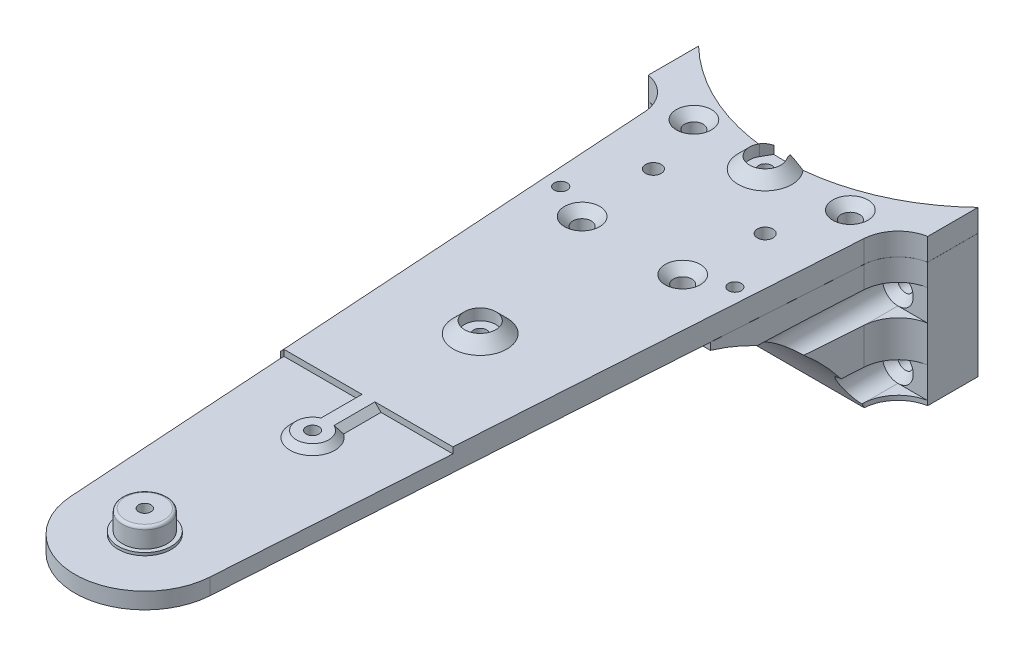
SolidWorks part; units mm, degrees
ref_plane "Front Plane" through (0, 0, 0) normal (0, 0, 1) x (1, 0, 0)
ref_plane "Top Plane" through (0, 0, 0) normal (0, 1, 0) x (1, 0, 0)
ref_plane "Right Plane" through (0, 0, 0) normal (1, 0, 0) x (0, 0, -1)
sketch "Sketch1" plane through (0, 0, 0) normal (0, 1, 0) x (1, 0, 0)
  line L0 (0, 0) -> (0, -150) construction
  line L1 (-22.2029, -1.4463) -> (-12.4736, -150.8125) construction
  line L2 (22.2029, -1.4462) -> (12.4736, -150.8125) construction
  line L3 (-12.4736, -150.8125) -> (-19.6328, -40.9037)
  line L4 (12.4736, -150.8125) -> (19.6328, -40.9037)
  line L5 (-25, -25.9037) -> (25, -25.9037) construction
  line L6 (-25, -25.9037) -> (-25, -34.9037)
  line L7 (25, -25.9037) -> (25, -34.9037)
  circle A0 centre (0, 0) radius 36 construction
  arc A1 (-12.4736, -150.8125) -> (12.4736, -150.8125) centre (0, -150) ccw
  circle A2 centre (0, 0) radius 19.5 construction
  circle A3 centre (0, 19.5) radius 2.75 construction
  circle A4 centre (0, 0) radius 22.25 construction
  arc A5 (-25, -25.9037) -> (25, -25.9037) centre (0, 0) ccw
  arc A6 (-25, -34.9037) -> (-19.6328, -40.9037) centre (-26.1442, -41.3278) cw
  arc A7 (25, -34.9037) -> (19.6328, -40.9037) centre (26.1442, -41.3278) ccw
  dimension "D1" = 72
  dimension "D3" = 25
  dimension "D4" = 39
  dimension "D5" = 5.5
  dimension "D2" = 150
  dimension "D6" = 50
  dimension "D7" = 9
  dimension "D8" = 15
extrude "Boss-Extrude1" add sketch "Sketch1" against normal blind 4
sketch "Sketch2" plane through (0, -4, 0) normal (0, -1, 0) x (1, 0, 0)
  line L0 (25, 34.9037) -> (25, 25.9037) construction
  line L1 (-25, 25.9037) -> (-25, 34.9037) construction
  line L2 (25, 34.9037) -> (25, 25.9037)
  line L3 (-25, 25.9037) -> (-25, 34.9037)
  line L4 (-19.6328, 40.9037) -> (19.6328, 40.9037)
  arc A0 (19.6328, 40.9037) -> (25, 34.9037) centre (26.1442, 41.3278) ccw construction
  arc A1 (25, 25.9037) -> (-25, 25.9037) centre (0, 0) ccw construction
  arc A2 (-25, 34.9037) -> (-19.6328, 40.9037) centre (-26.1442, 41.3278) ccw construction
  arc A3 (19.6328, 40.9037) -> (25, 34.9037) centre (26.1442, 41.3278) ccw
  arc A4 (25, 25.9037) -> (-25, 25.9037) centre (0, 0) ccw
  arc A5 (-25, 34.9037) -> (-19.6328, 40.9037) centre (-26.1442, 41.3278) ccw
extrude "Boss-Extrude2" add sketch "Sketch2" along normal offset from surface (22.2378 mm away) 26.2378 up to face at (0, 0, 65.6223)
ref_plane "Plane1" through (0, 0, 34.9037) normal (0, 0, 1) x (1, 0, 0)
fillet "Fillet2" radius 40 1 edges at (0, -4, 40.9037)
sketch "Sketch3" plane through (0, 0, 34.9037) normal (0, 0, 1) x (1, 0, 0)
  line L0 (25, 0) -> (-25, 0) construction
  line L1 (-19.6636, -22.6878) -> (19.6636, -22.6878) construction
  line L2 (-19.6636, -22.6878) -> (-19.6636, -10.6878) construction
  line L3 (-19.6636, -10.6878) -> (19.6636, -10.6878) construction
  line L4 (19.6636, -22.6878) -> (19.6636, -10.6878) construction
  line L5 (-19.6636, -22.6878) -> (19.6636, -10.6878) construction
  line L6 (-19.6636, -10.6878) -> (19.6636, -22.6878) construction
  line L7 (-19.6636, -7.9378) -> (-25, -7.9378)
  line L8 (-25, -7.9378) -> (-25, -13.4378)
  line L9 (-25, -13.4378) -> (-19.6636, -13.4378)
  line L10 (-25, -26.2378) -> (-25, 0) construction
  line L11 (0, -16.6878) -> (-25, -16.6878) construction
  line L12 (-25, -25.4378) -> (-25, -19.9378)
  line L13 (-25, -19.9378) -> (-19.6636, -19.9378)
  line L14 (-19.6636, -25.4378) -> (-25, -25.4378)
  line L15 (0, -16.6878) -> (0, 0) construction
  line L16 (19.6636, -25.4378) -> (25, -25.4378)
  line L17 (25, -19.9378) -> (19.6636, -19.9378)
  line L18 (25, -25.4378) -> (25, -19.9378)
  line L19 (25, -13.4378) -> (19.6636, -13.4378)
  line L20 (25, -7.9378) -> (25, -13.4378)
  line L21 (19.6636, -7.9378) -> (25, -7.9378)
  arc A0 (-19.6636, -13.4378) -> (-19.6636, -7.9378) centre (-19.6636, -10.6878) ccw
  arc A4 (-19.6636, -19.9378) -> (-19.6636, -25.4378) centre (-19.6636, -22.6878) cw
  arc A5 (19.6636, -19.9378) -> (19.6636, -25.4378) centre (19.6636, -22.6878) ccw
  arc A6 (19.6636, -13.4378) -> (19.6636, -7.9378) centre (19.6636, -10.6878) cw
  point P0 (0, -16.6878)
  dimension "D4" = 5.5
  dimension "D1" = 10.6878
  dimension "D2" = 12
  dimension "D3" = 39.3272
extrude "Cut-Extrude1" cut sketch "Sketch3" along normal through all
chamfer "Chamfer1" [suppressed] distance 2.75 angle 60
hole_wizard "CSK for M2.5 Flat Head Machine Screw1" positions "Sketch5" profile "Sketch6" countersink size "M2.5" standard "ANSI Metric" end condition through all
sketch "Sketch5" plane through (0, 0, 34.9037) normal (0, 0, 1) x (1, 0, 0)
  point P0 (19.6636, -22.6878)
  point P3 (-19.6636, -22.6878)
  point P6 (-19.6636, -10.6878)
  point P9 (19.6636, -10.6878)
sketch "Sketch6" plane through (19.6636, -22.6878, 34.9037) normal (1, 0, 0) x (0, -1, 0)
  line L0 (0, 0) -> (0, 9)
  line L1 (0, 9) -> (1.4, 9)
  line L2 (1.4, 9) -> (1.4, 1.35)
  line L3 (1.4, 1.35) -> (2.75, 0)
  line L5 (2.75, 0) -> (0, 0)
  line L6 (-1.4, 1.35) -> (-2.75, 0) construction
  line L11 (0, -6.35) -> (0, 107.95) construction
  dimension "Thru Hole Dia." = 2.8
  dimension "Thru Hole Depth" = 9
  dimension "Near C'Sink Dia." = 5.5
  dimension "Near C'Sink Angle" = 90
sketch "Sketch8" plane through (0, 0, 0) normal (0, 1, 0) x (1, 0, 0)
  line L1 (1.0164, -92.5616) -> (1.0209, -117.4381) construction
  line L2 (-0.9836, -92.5619) -> (-0.9791, -117.4384) construction
  line L3 (15.1322, -109.9973) -> (15.1322, -176.6324)
  line L4 (15.1322, -176.6324) -> (-15.0896, -176.6324)
  line L5 (-15.0896, -176.6324) -> (-15.0896, -109.9973)
  line L29 (-0.9805, -109.9973) -> (-0.9791, -117.4384)
  line L30 (1.0195, -109.9973) -> (1.0209, -117.4381)
  line L31 (1.0195, -109.9973) -> (15.1322, -109.9973)
  line L72 (-15.0896, -109.9973) -> (-0.9805, -109.9973)
  arc A4 (-0.9791, -117.4384) -> (1.0209, -117.4381) centre (0.0213, -120) ccw construction
  arc A8 (-0.9791, -117.4384) -> (1.0209, -117.4381) centre (0.0213, -120) ccw
  point P0 (0.0213, -176.6324)
  dimension "D2" = 5.5
extrude "Cut-Extrude3" cut sketch "Sketch8" against normal blind 1.09
sketch "Sketch9" plane through (0, -4, 0) normal (0, -1, 0) x (1, 0, 0)
  line L0 (-17.2982, 76.7436) -> (17.2982, 76.7436)
  line L1 (17.2982, 76.7436) -> (17.9496, 66.7436)
  line L2 (17.9496, 66.7436) -> (-17.9496, 66.7436)
  line L3 (-17.9496, 66.7436) -> (-17.2982, 76.7436)
  line L4 (-17.2982, 76.7436) -> (-12.4736, 150.8125) construction
  line L5 (12.4736, 150.8125) -> (17.2982, 76.7436) construction
  dimension "D1" = 10
extrude "Cut-Extrude4" cut sketch "Sketch9" along normal through all
sketch "Sketch11" plane through (0, -4, 0) normal (0, -1, 0) x (1, 0, 0)
  circle A0 centre (0, 0) radius 161
extrude "Cut-Extrude5" cut sketch "Sketch11" along normal blind 0.01
sketch "Sketch12" plane through (0, 0, 0) normal (0, 1, 0) x (1, 0, 0)
  line L0 (-17.9496, -66.7436) -> (17.9496, -66.7436) construction
  line L1 (-17.9496, -66.7436) -> (17.9496, -66.7436) construction
  line L3 (-9, -62.7436) -> (9, -62.7436) construction
  line L4 (-9, -62.7436) -> (-14, -37.7436) construction
  line L5 (-14, -37.7436) -> (14, -37.7436) construction
  line L6 (9, -62.7436) -> (14, -37.7436) construction
  line L7 (-9, -62.7436) -> (14, -37.7436) construction
  line L8 (-14, -37.7436) -> (9, -62.7436) construction
  circle A0 centre (-14, -37.7436) radius 1.65
  circle A1 centre (14, -37.7436) radius 1.65
  circle A2 centre (-9, -62.7436) radius 1.65
  circle A3 centre (9, -62.7436) radius 1.65
  point P2 (0, -52.961)
  point P15 (0, -62.7436)
  dimension "D1" = 3.3
  dimension "D2" = 4
  dimension "D3" = 28
  dimension "D4" = 25
  dimension "D5" = 18
extrude "Cut-Extrude6" cut sketch "Sketch12" against normal blind 8.25
ref_plane "Plane2" through (0, -5.2702, 0) normal (0, 1, 0) x (1, 0, 0)
sketch "Sketch13" plane through (0, -5.2702, 0) normal (0, 1, 0) x (1, 0, 0)
  line L0 (0, 0) -> (0, -36) construction
  line L1 (-11.75, -59.9936) -> (-6.25, -59.9936)
  line L2 (-11.75, -59.9936) -> (-11.75, -65.4936)
  line L3 (-11.75, -65.4936) -> (-6.25, -65.4936) construction
  line L4 (-6.25, -59.9936) -> (-6.25, -65.4936)
  line L5 (-11.75, -59.9936) -> (-6.25, -65.4936) construction
  line L6 (-11.75, -65.4936) -> (-6.25, -59.9936) construction
  line L7 (-6.25, -65.4936) -> (-6.25, -66.7436)
  line L8 (-17.9496, -66.7436) -> (17.9496, -66.7436) construction
  line L9 (-6.25, -66.7436) -> (-11.75, -66.7436)
  line L10 (-11.75, -66.7436) -> (-11.75, -65.4936)
  line L11 (6.25, -66.7436) -> (11.75, -66.7436)
  line L12 (6.25, -65.4936) -> (6.25, -66.7436)
  line L13 (6.25, -59.9936) -> (6.25, -65.4936)
  line L14 (11.75, -59.9936) -> (6.25, -59.9936)
  line L15 (11.75, -59.9936) -> (11.75, -65.4936)
  line L16 (11.75, -66.7436) -> (11.75, -65.4936)
  arc A0 (-25, -25.9037) -> (25, -25.9037) centre (0, 0) ccw construction
  point P0 (-9, -62.7436)
  dimension "D1" = 5.5
extrude "Cut-Extrude7" cut sketch "Sketch13" against normal blind 8.5
sketch "Sketch14" plane through (0, -8.25, 0) normal (0, 1, 0) x (1, 0, 0)
  line L0 (0, 0) -> (0, -36) construction
  line L1 (-14, -37.7436) -> (0, 0) construction
  line L2 (-15.681, -34.0804) -> (-10.3368, -36.0627) construction
  line L3 (-15.681, -34.0804) -> (-17.6632, -39.4246)
  line L4 (-17.6632, -39.4246) -> (-12.319, -41.4069)
  line L5 (-10.3368, -36.0627) -> (-12.319, -41.4069)
  line L6 (-15.681, -34.0804) -> (-12.319, -41.4069) construction
  line L7 (-17.6632, -39.4246) -> (-10.3368, -36.0627) construction
  line L8 (-15.681, -34.0804) -> (-15.1525, -32.6558)
  line L9 (-15.1525, -32.6558) -> (-9.8083, -34.6381)
  line L10 (-9.8083, -34.6381) -> (-10.3368, -36.0627)
  line L11 (15.1525, -32.6558) -> (9.8083, -34.6381)
  line L12 (15.681, -34.0804) -> (15.1525, -32.6558)
  line L13 (15.681, -34.0804) -> (17.6632, -39.4246)
  line L14 (17.6632, -39.4246) -> (12.319, -41.4069)
  line L15 (10.3368, -36.0627) -> (12.319, -41.4069)
  line L16 (9.8083, -34.6381) -> (10.3368, -36.0627)
  arc A0 (-25, -25.9037) -> (25, -25.9037) centre (0, 0) ccw construction
  point P6 (-14, -37.7436)
  dimension "D1" = 5.7
extrude "Cut-Extrude8" cut sketch "Sketch14" along normal blind 2
hole_wizard "CSK for M3 Flat Head Machine Screw1" positions "Sketch15" profile "Sketch16" countersink size "M3" standard "ANSI Metric"
sketch "Sketch15" plane through (0, 0, 0) normal (0, 1, 0) x (1, 0, 0)
  point P0 (-14, -37.7436)
  point P3 (14, -37.7436)
  point P6 (9, -62.7436)
  point P9 (-9, -62.7436)
sketch "Sketch16" plane through (-14, 0, 37.7436) normal (1, 0, 0) x (0, 0, 1)
  line L0 (0, 0) -> (0, 8.9914)
  line L1 (0, 8.9914) -> (1.65, 8)
  line L2 (1.65, 8) -> (1.65, 1.5)
  line L3 (1.65, 1.5) -> (3.15, 0)
  line L5 (3.15, 0) -> (0, 0)
  line L6 (-1.65, 1.5) -> (-3.15, 0) construction
  line L10 (0, 8.9914) -> (-1.65, 8) construction
  line L11 (0, -6.35) -> (0, 107.95) construction
  dimension "Hole Dia." = 3.3
  dimension "Hole Depth" = 8
  dimension "Near C'Sink Dia." = 6.3
  dimension "Near C'Sink Angle" = 90
  dimension "Drill Angle" = 118
sketch "Sketch18" plane through (0, -4, 0) normal (0, -1, 0) x (1, 0, 0)
  circle A1 centre (0.0071, 39) radius 2.75
  circle A2 centre (0.0071, 39) radius 2.75 construction
  circle A3 centre (0.016, 90) radius 2.8 construction
  arc A5 (1.0209, 117.4381) -> (-0.9791, 117.4384) centre (0.0213, 120) ccw construction
  circle A9 centre (-15.5725, 60.0029) radius 1.15
  circle A11 centre (-15.5725, 60.0029) radius 2.75
  circle A12 centre (-15.5725, 60.0029) radius 2.75 construction
  circle A13 centre (15.5944, 59.9971) radius 1.15
  circle A15 centre (0.0071, 39) radius 1.15
  circle A17 centre (15.5944, 59.9971) radius 2.75
  circle A18 centre (15.5944, 59.9971) radius 2.75 construction
  arc A19 (1.0209, 117.4381) -> (-0.9791, 117.4384) centre (0.0213, 120) ccw construction
  circle A20 centre (0.0213, 120) radius 1.15
  circle A21 centre (0.016, 90) radius 2.8 construction
  circle A22 centre (0.016, 90) radius 1.15
  dimension "D2" = 2.3
  dimension "D1" = 0
  dimension "D6" = 0
  dimension "D9" = 0
extrude "Cut-Extrude9" cut sketch "Sketch18" against normal through all
sketch "Sketch19" plane through (0, -4, 0) normal (0, -1, 0) x (1, 0, 0)
  line L1 (1.4503, 122.475) -> (-1.4076, 122.475)
  line L2 (-1.4076, 122.475) -> (-2.8366, 120)
  line L3 (-2.8366, 120) -> (-1.4076, 117.525)
  line L4 (-1.4076, 117.525) -> (1.4503, 117.525)
  line L5 (1.4503, 117.525) -> (2.8792, 120)
  line L6 (2.8792, 120) -> (1.4503, 122.475)
  line L7 (1.4449, 92.475) -> (-1.413, 92.475)
  line L8 (-1.413, 92.475) -> (-2.8419, 90)
  line L9 (-2.8419, 90) -> (-1.413, 87.525)
  line L10 (-1.413, 87.525) -> (1.4449, 87.525)
  line L11 (1.4449, 87.525) -> (2.8739, 90)
  line L12 (2.8739, 90) -> (1.4449, 92.475)
  line L13 (-12.7206, 59.8171) -> (-13.9857, 62.3797)
  line L14 (-13.9857, 62.3797) -> (-16.8375, 62.5655)
  line L15 (-16.8375, 62.5655) -> (-18.4243, 60.1886) construction
  line L16 (-18.4243, 60.1886) -> (-17.1593, 57.626) construction
  line L17 (-17.1593, 57.626) -> (-14.3074, 57.4402)
  line L18 (-14.3074, 57.4402) -> (-12.7206, 59.8171)
  line L19 (2.4786, 37.5649) -> (2.4857, 40.4228)
  line L20 (2.4857, 40.4228) -> (0.0143, 41.8579)
  line L21 (0.0143, 41.8579) -> (-2.4643, 40.4351)
  line L22 (-2.4643, 40.4351) -> (-2.4714, 37.5772)
  line L23 (-2.4714, 37.5772) -> (0, 36.1421) construction
  line L24 (0, 36.1421) -> (2.4786, 37.5649) construction
  line L25 (0, 0) -> (0, 162.5) construction
  line L26 (-18.4243, 60.1886) -> (-15.5725, 60.0029) construction
  line L27 (-19.6328, 40.9037) -> (-12.4736, 150.8125) construction
  line L28 (-16.8375, 62.5655) -> (-18.2159, 62.6553)
  line L29 (-18.2159, 62.6553) -> (-18.5377, 57.7158)
  line L30 (-18.5377, 57.7158) -> (-17.1593, 57.626)
  line L31 (18.2159, 62.6553) -> (18.5377, 57.7158)
  line L32 (16.8375, 62.5655) -> (18.2159, 62.6553)
  line L33 (13.9857, 62.3797) -> (16.8375, 62.5655)
  line L34 (12.7206, 59.8171) -> (13.9857, 62.3797)
  line L35 (14.3074, 57.4402) -> (12.7206, 59.8171)
  line L36 (17.1593, 57.626) -> (14.3074, 57.4402)
  line L37 (18.5377, 57.7158) -> (17.1593, 57.626)
  line L38 (-2.4714, 37.5772) -> (-2.4714, 35.9151)
  line L39 (-2.4714, 35.9151) -> (2.4786, 35.9146)
  line L40 (2.4786, 35.9146) -> (2.4786, 37.5649)
  circle A0 centre (0.0213, 120) radius 2.475 construction
  circle A1 centre (0.016, 90) radius 2.475 construction
  circle A2 centre (-15.5725, 60.0029) radius 2.475 construction
  circle A3 centre (0.0071, 39) radius 2.475 construction
  arc A4 (12.4736, 150.8125) -> (-12.4736, 150.8125) centre (0, 150) ccw construction
  arc A5 (25, 25.9037) -> (-25, 25.9037) centre (0, 0) ccw construction
  circle A6 centre (0.0213, 120) radius 1.15 construction
  circle A7 centre (0.016, 90) radius 1.15 construction
  dimension "D1" = 4.95
extrude "Cut-Extrude10" [suppressed] cut sketch "Sketch19" against normal blind 2.1
sketch "Sketch20" plane through (0, -1.09, 0) normal (0, 1, 0) x (1, 0, 0)
  circle A0 centre (0, -150) radius 4.75
  dimension "D1" = 9.5
extrude "Boss-Extrude3" add sketch "Sketch20" along normal blind 0.5
sketch "Sketch21" plane through (0, -0.59, 0) normal (0, 1, 0) x (1, 0, 0)
  circle A0 centre (0, -150) radius 4
  dimension "D1" = 8
extrude "Boss-Extrude4" add sketch "Sketch21" along normal blind 3.5
fillet "Fillet4" radius 0.5 1 edges at (0, 2.91, 154)
sketch "Sketch22" plane through (0, 0, 0) normal (0, 1, 0) x (1, 0, 0)
  line L0 (0, 0) -> (0, -150) construction
  circle A0 centre (0, 0) radius 50 construction
  arc A1 (-25, -25.9037) -> (25, -25.9037) centre (0, 0) ccw construction
  circle A2 centre (10, -48.9898) radius 1.4
  circle A3 centre (10, -48.9898) radius 3.5 construction
  circle A4 centre (-10, -48.9898) radius 1.4
  dimension "D1" = 100
  dimension "D2" = 2.8
  dimension "D4" = 7
  dimension "D3" = 10
extrude "Cut-Extrude12" cut sketch "Sketch22" against normal through all contours A2 | A4
sketch "Sketch24" plane through (0, 2.91, 0) normal (0, -1, 0) x (1, 0, 0)
  circle A0 centre (0, 150) radius 1.1
  dimension "D1" = 2.2
extrude "Cut-Extrude13" cut sketch "Sketch24" along normal through all
ref_plane "Plane3" through (0, 0, 36) normal (0, 0, -1) x (-1, 0, 0)
sketch "Sketch25" plane through (0, 0, 36) normal (0, 0, -1) x (-1, 0, 0)
  line L0 (-19.6636, -22.6878) -> (19.6636, -22.6878) construction
  line L1 (0, 0) -> (0, -22.6878) construction
  line L2 (-14.13, -15.5878) -> (-10.13, -15.5878)
  line L3 (-14.13, -15.5878) -> (-14.13, -18.5878)
  line L4 (-14.13, -18.5878) -> (-10.13, -18.5878)
  line L5 (-10.13, -15.5878) -> (-10.13, -18.5878)
  line L6 (10.13, -15.5878) -> (10.13, -18.5878)
  line L7 (14.13, -18.5878) -> (10.13, -18.5878)
  line L8 (14.13, -15.5878) -> (14.13, -18.5878)
  line L9 (14.13, -15.5878) -> (10.13, -15.5878)
  dimension "D1" = 7.1
  dimension "D2" = 20.26
  dimension "D3" = 4
  dimension "D4" = 3
extrude "Boss-Extrude6" add sketch "Sketch25" along normal blind 3
chamfer "Chamfer2" distance 1.8 angle 45 2 edges at (-12.1512, -18.5878, 33.8873) (12.1512, -18.5878, 33.8873)
chamfer "Chamfer3" [suppressed] distance 2 angle 45
chamfer "Chamfer4" distance 1.25 angle 45 3 edges at (0.0218, -1.09, 122.75) (-0.9798, -1.09, 113.7179) (1.0202, -1.09, 113.7177)
sketch "Sketch26" [suppressed] plane through (0, -4, 0) normal (0, -1, 0) x (1, 0, 0)
  line L0 (-18.2159, 62.6553) -> (-12.4736, 150.8125) construction
  line L1 (12.4736, 150.8125) -> (18.2159, 62.6553) construction
  line L2 (-18.2159, 62.6553) -> (-17.9496, 66.7436)
  line L3 (17.9496, 66.7436) -> (18.2159, 62.6553)
  line L4 (-17.9496, 66.7436) -> (17.9496, 66.7436) construction
  line L5 (-17.9496, 66.7436) -> (-15.9454, 66.7436)
  line L6 (18.2159, 62.6553) -> (16.2202, 62.5253)
  line L7 (16.2202, 62.5253) -> (15.9454, 66.7436)
  line L8 (-18.2159, 62.6553) -> (-16.2202, 62.5253)
  line L9 (-10.4778, 150.6825) -> (-16.2202, 62.5253) construction
  line L10 (-16.2202, 62.5253) -> (-15.9454, 66.7436)
  line L11 (15.9454, 66.7436) -> (17.9496, 66.7436)
extrude "Boss-Extrude7" [suppressed] add sketch "Sketch26" against normal up to surface (4 mm away) up to face at (-1.1512, 0, 77.1191)
sketch "Sketch29" plane through (0, 0, 0) normal (0, 1, 0) x (1, 0, 0)
  line L0 (-19.0027, -30.5761) -> (-10.8155, -156.2669) construction
  line L1 (-19.6328, -40.9037) -> (-15.0896, -110.6516) construction
  line L2 (-17.2328, -57.7482) -> (-17.3757, -55.5544) construction
  line L3 (-16.9263, -62.4538) -> (-16.7834, -64.6476) construction
  line L4 (0, 0) -> (0, -162.5) construction
  line L5 (16.9263, -62.4538) -> (16.7834, -64.6476) construction
  line L6 (17.2328, -57.7482) -> (17.3757, -55.5544) construction
  line L7 (-2.4177, -37.6) -> (-1.4765, -35.9697)
  line L8 (2.432, -37.6) -> (1.4919, -35.9691)
  circle A0 centre (0.016, -90) radius 2.8
  circle A1 centre (0.016, -90) radius 4.8
  arc A2 (-16.9263, -62.4538) -> (-17.2328, -57.7482) centre (-15.5725, -60.0029) ccw construction
  arc A4 (-25, -25.9037) -> (25, -25.9037) centre (0, 0) ccw construction
  arc A5 (-12.4736, -150.8125) -> (12.4736, -150.8125) centre (0, -150) ccw construction
  arc A6 (-10.7745, -60.141) -> (-17.3757, -55.5544) centre (-15.5725, -60.0029) ccw construction
  circle A7 centre (-9, -62.7436) radius 3.15 construction
  arc A8 (-10.7745, -60.141) -> (-12.0978, -63.3145) centre (-9, -62.7436) ccw construction
  arc A9 (-2.4177, -37.6) -> (2.432, -37.6) centre (0.0071, -39) ccw
  arc A10 (-16.7834, -64.6476) -> (-12.0978, -63.3145) centre (-15.5725, -60.0029) ccw construction
  arc A11 (16.7834, -64.6476) -> (12.0978, -63.3145) centre (15.5725, -60.0029) cw construction
  arc A12 (10.7745, -60.141) -> (12.0978, -63.3145) centre (9, -62.7436) cw construction
  arc A13 (10.7745, -60.141) -> (17.3757, -55.5544) centre (15.5725, -60.0029) cw construction
  arc A14 (16.9263, -62.4538) -> (17.2328, -57.7482) centre (15.5725, -60.0029) cw construction
  arc A15 (-3.5889, -35.8207) -> (3.6021, -35.8193) centre (0.0071, -39) ccw
  arc A16 (-25, -25.9037) -> (-19.0027, -30.5761) centre (0, 0) ccw
  arc A17 (-3.5889, -35.8207) -> (-1.4765, -35.9697) centre (0, 0) ccw
  arc A18 (1.4919, -35.9691) -> (3.6021, -35.8193) centre (0, 0) ccw
  point P36 (0.7013, -35.9697)
  point P42 (2.5564, -37.8419)
  point P44 (-1.7495, -35.9575)
  point P46 (2.4177, -37.7093)
  point P47 (0, 0)
  point P48 (0, 0)
  point P49 (0, 0)
  point P50 (0, 0)
  point P51 (0, 0)
  arc M17 (25, -25.9037) -> (-25, -25.9037) centre (0, 0) cw
  dimension "D1" = 5.6
  dimension "D2" = 2
  dimension "D3" = 5.6
  dimension "D5" = 2
  dimension "D6" = 5.6
  dimension "D7" = 2
  dimension "D4" = 1.3
  dimension "D8" = 30
extrude "Boss-Extrude8" add sketch "Sketch29" along normal blind 2 contours A15 L8 A9 L7 M17 | A1 A0 region at (0.0071, 0, 41.9248) region at (-4.6483, 0, 90)
chamfer "Chamfer5" distance 2 angle 45 2 edges at (0.008, 2, 43.8) (0.016, 2, 94.8)
